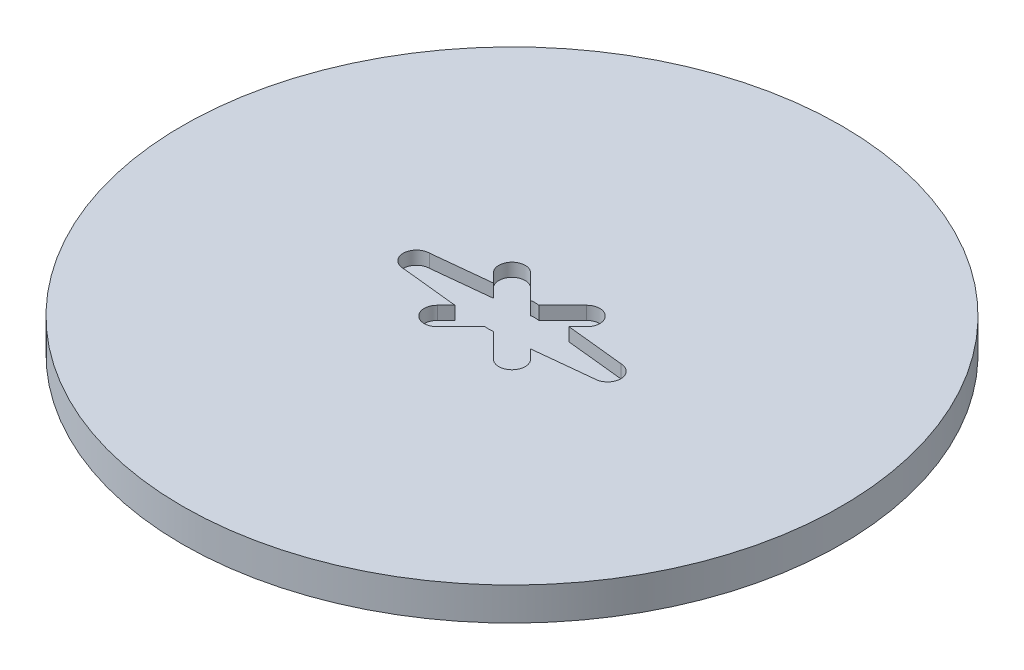
SolidWorks part; units mm, degrees
ref_plane "Front Plane" through (0, 0, 0) normal (0, 0, 1) x (1, 0, 0)
ref_plane "Top Plane" through (0, 0, 0) normal (0, 1, 0) x (1, 0, 0)
ref_plane "Right Plane" through (0, 0, 0) normal (1, 0, 0) x (0, 0, -1)
sketch "Sketch1" plane through (0, 0, 0) normal (0, 1, 0) x (1, 0, 0)
  circle A0 centre (0, 0) radius 50
  dimension "D1" = 100
extrude "Boss-Extrude1" add sketch "Sketch1" along normal blind 5
sketch "Sketch2" plane through (0, 5, 0) normal (0, 1, 0) x (1, 0, 0)
  line L0 (-14.5, -2) -> (-5.7456, -2.9172)
  line L1 (14.5, 2) -> (5.7456, 2.9172)
  line L2 (14.5, -2) -> (5.7456, -2.9172)
  line L3 (4.2426, 7.0711) -> (0.6168, 3.4452)
  line L4 (-14.5, 2) -> (-5.7456, 2.9172)
  line L5 (4.2426, -7.0711) -> (0.6168, -3.4452)
  line L6 (7.0711, -4.2426) -> (5.7456, -2.9172)
  line L7 (-7.0711, -4.2426) -> (-5.7456, -2.9172)
  line L8 (7.0711, 4.2426) -> (5.7456, 2.9172)
  line L9 (-4.2426, -7.0711) -> (-0.6168, -3.4452)
  line L10 (-4.2426, 7.0711) -> (-0.6168, 3.4452)
  line L11 (-7.0711, 4.2426) -> (-5.7456, 2.9172)
  arc A0 (-0.6168, -3.4452) -> (0.6168, -3.4452) centre (0, 0) ccw
  arc A1 (14.5, -2) -> (14.5, 2) centre (14.5, 0) ccw
  arc A2 (7.0711, 4.2426) -> (4.2426, 7.0711) centre (5.6569, 5.6569) ccw
  arc A3 (-14.5, 2) -> (-14.5, -2) centre (-14.5, 0) ccw
  arc A4 (4.2426, -7.0711) -> (7.0711, -4.2426) centre (5.6569, -5.6569) ccw
  arc A5 (-7.0711, -4.2426) -> (-4.2426, -7.0711) centre (-5.6569, -5.6569) ccw
  arc A6 (-4.2426, 7.0711) -> (-7.0711, 4.2426) centre (-5.6569, 5.6569) ccw
  arc A7 (0.6168, 3.4452) -> (-0.6168, 3.4452) centre (0, 0) ccw
  point P18 (0, 0)
  point P24 (0, 0)
  point P38 (0, 0)
  dimension "D1" = 7
  dimension "D2" = 4
  dimension "D3" = 4
  dimension "D4" = 2
  dimension "D5" = 4
extrude "Cut-Extrude1" cut sketch "Sketch2" against normal blind 2
